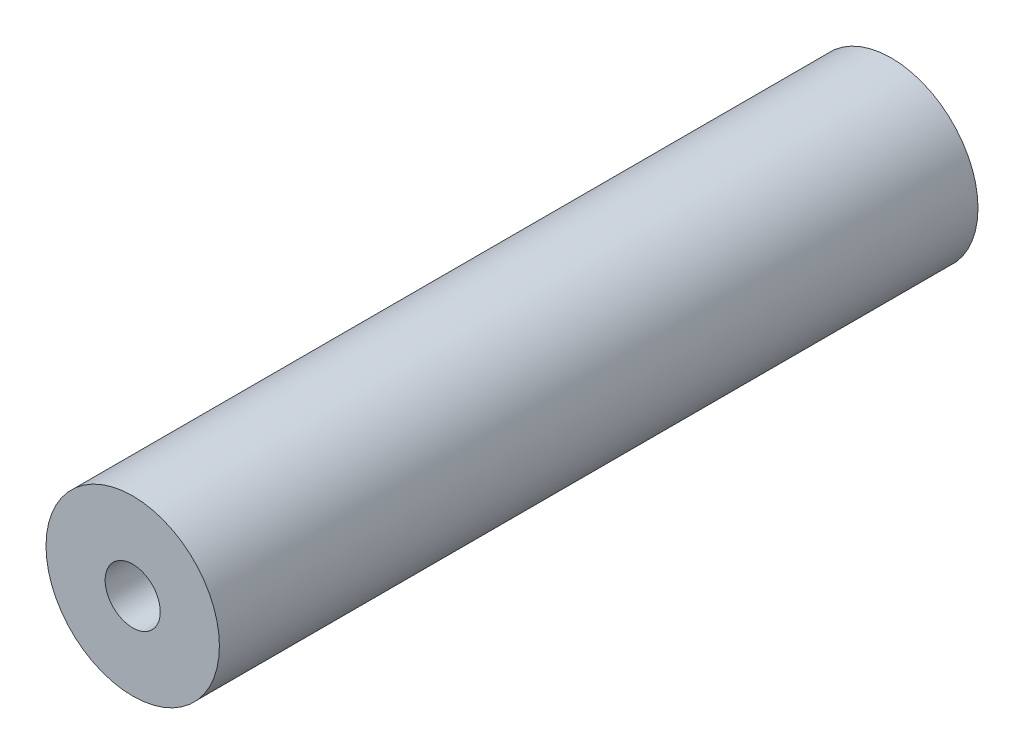
SolidWorks part; units mm, degrees
ref_plane "Front Plane" through (0, 0, 0) normal (0, 0, 1) x (1, 0, 0)
ref_plane "Top Plane" through (0, 0, 0) normal (0, 1, 0) x (1, 0, 0)
ref_plane "Right Plane" through (0, 0, 0) normal (1, 0, 0) x (0, 0, -1)
sketch "Sketch1" plane through (0, 0, 0) normal (0, 0, 1) x (1, 0, 0)
  circle A1 centre (0, 0) radius 6.35
  dimension "D2" = 12.7
extrude "Boss-Extrude1" add sketch "Sketch1" along normal mid plane 55.5625 contours A1 region at (0, 0, 0)
hole_wizard "#10-32 Tapped Hole1" positions "3DSketch1" profile "Sketch2" tap size "#10-32" standard "ANSI Inch"
sketch3d "3DSketch1"
  line L0 (0, 0, 27.7812) -> (0, 0, -27.7812) construction
  point P0 (0, 0, -27.7812)
  point P4 (0, 0, 27.7812)
sketch "Sketch2" plane through (0, 0, -27.7812) normal (1, 0, 0) x (0, 1, 0)
  line L0 (0, 0) -> (0, 13.2428)
  line L1 (0, 13.2428) -> (2.0193, 12.0294)
  line L2 (2.0193, 12.0294) -> (2.0193, 0)
  line L5 (2.0193, 0) -> (0, 0)
  line L10 (0, 13.2428) -> (-2.0193, 12.0294) construction
  line L11 (0, -6.35) -> (0, 107.95) construction
  dimension "Tap Drill Dia." = 4.0386
  dimension "Tap Drill Depth" = 12.0294
  dimension "Drill Angle" = 118
cosmetic thread "Hole Thread1" parameters "D1"=9.652, "D2"=4.826
cosmetic thread "Hole Thread2" parameters "D1"=9.652, "D2"=4.826
